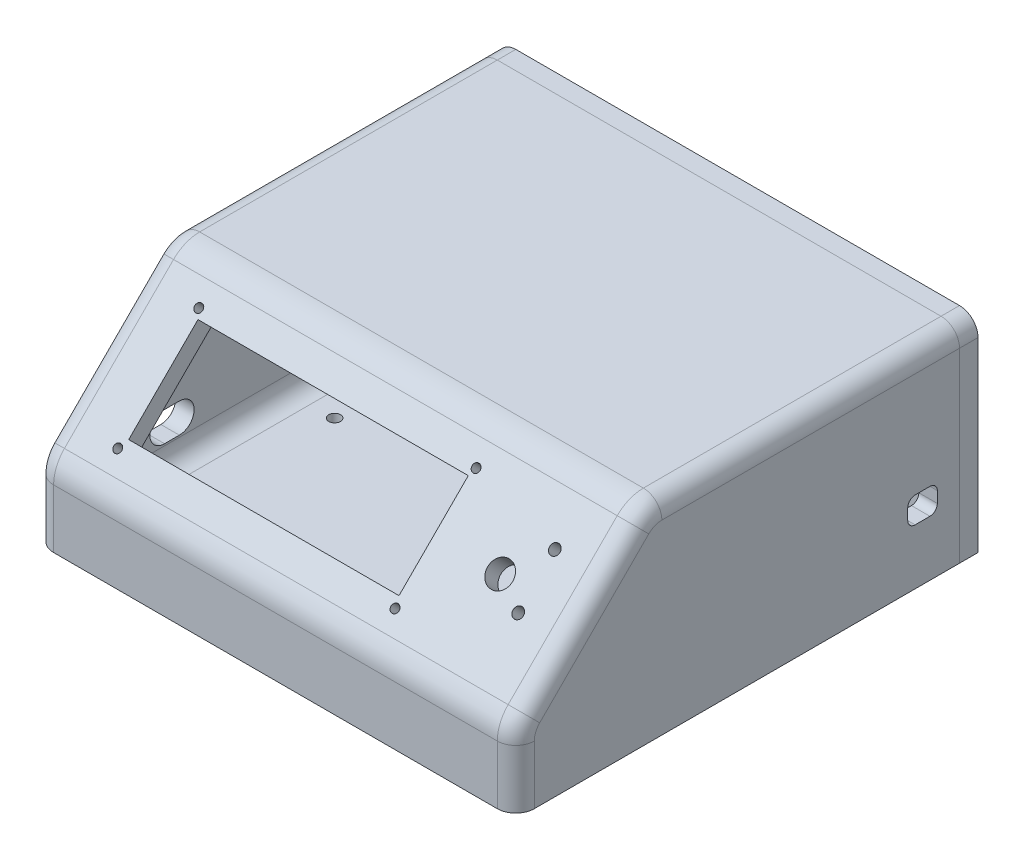
SolidWorks part; units mm, degrees
ref_plane "Front Plane" through (0, 0, 0) normal (0, 0, 1) x (1, 0, 0)
ref_plane "Top Plane" through (0, 0, 0) normal (0, 1, 0) x (1, 0, 0)
ref_plane "Right Plane" through (0, 0, 0) normal (1, 0, 0) x (0, 0, -1)
sketch "Sketch2" plane through (0, 0, 0) normal (1, 0, 0) x (0, 0, -1)
  line L0 (0, 0) -> (0, 20)
  line L1 (0, 20) -> (35.3553, 55.3553)
  line L2 (35.3553, 55.3553) -> (120, 55.3553)
  line L3 (120, 55.3553) -> (120, 0)
  line L4 (120, 0) -> (0, 0)
  dimension "D1" = 20
  dimension "D2" = 50
  dimension "D3" = 135
  dimension "D4" = 120
extrude "Boss-Extrude1" add sketch "Sketch2" along normal blind 130
shell "Shell1" thickness 5 removed face at (65, 27.6777, -120)
sketch "Sketch3" plane through (0, 10, 10) normal (0, 0.7071, 0.7071) x (1, 0, 0)
  line L0 (0, 64.1421) -> (0, 14.1421) construction
  line L1 (17, 52.3921) -> (90.1, 52.3921)
  line L2 (17, 52.3921) -> (17, 25.8921)
  line L3 (17, 25.8921) -> (90.1, 25.8921)
  line L4 (90.1, 52.3921) -> (90.1, 25.8921)
  circle A0 centre (108.1, 39.1421) radius 3.4
  point P6 (0, 39.1421)
  point P7 (17, 39.1421)
  point P11 (90.1, 39.1421)
  dimension "D3" = 6.8
  dimension "D1" = 73.1
  dimension "D2" = 26.5
  dimension "D4" = 18
  dimension "D5" = 17
extrude "Cut-Extrude1" cut sketch "Sketch3" against normal up to surface (5 mm away) up to face at (65, 34.1421, -21.2132)
fillet "Fillet1" radius 10 5 edges at (65, 20, 0) (65, 55.3553, -35.3553) (65, 50.3553, -37.4264) (65, 5, -5) (65, 17.9289, -5)
fillet "Fillet2" radius 5 10 edges at (0, 55.3553, -79.7487) (0, 54.5941, -35.6706) (0, 37.6777, -17.6777) (0, 19.6847, -0.7612) (130, 55.3553, -79.7487) (130, 54.5941, -35.6706) (130, 37.6777, -17.6777) (130, 19.6847, -0.7612) (0, 7.9289, 0) (130, 7.9289, 0)
sketch "Sketch4" plane through (130, 0, 0) normal (1, 0, 0) x (0, 0, -1)
  line L0 (5, 0) -> (120, 0) construction
  line L1 (108, 22) -> (112, 22)
  line L2 (106, 20) -> (106, 17)
  line L3 (108, 15) -> (112, 15)
  line L4 (114, 20) -> (114, 17)
  line L5 (120, 0) -> (120, 50.3553) construction
  arc A0 (106, 17) -> (108, 15) centre (108, 17) ccw
  arc A1 (112, 15) -> (114, 17) centre (112, 17) ccw
  arc A2 (112, 22) -> (114, 20) centre (112, 20) cw
  arc A3 (108, 22) -> (106, 20) centre (108, 20) ccw
  point P8 (114, 15)
  point P11 (114, 22)
  point P14 (106, 22)
  point P15 (63.3615, 10.7328)
  dimension "D3" = 2
  dimension "D1" = 8
  dimension "D2" = 7
  dimension "D4" = 15
  dimension "D5" = 6
extrude "Cut-Extrude2" cut sketch "Sketch4" against normal up to surface (5 mm away) up to face at (125, 27.4827, -48.7525)
fillet "Fillet3" radius 5 12 edges at (125, 7.7176, -8.1468) (125, 17.8922, -5.8816) (125, 34.1421, -21.2132) (125, 49.5941, -37.7417) (5, 7.7176, -8.1468) (5, 17.8922, -5.8816) (5, 34.1421, -21.2132) (5, 49.5941, -37.7417) (125, 5, -67.5) (125, 50.3553, -80.7843) (5, 5, -67.5) (5, 50.3553, -80.7843)
sketch "Sketch5" plane through (0, 10, 10) normal (0, 0.7071, 0.7071) x (1, 0, 0)
  line L0 (102.2, 33.1421) -> (114, 45.1421) construction
  line L1 (102.2, 45.1421) -> (114, 45.1421) construction
  line L2 (102.2, 45.1421) -> (102.2, 33.1421) construction
  line L3 (102.2, 33.1421) -> (114, 33.1421) construction
  line L4 (114, 45.1421) -> (114, 33.1421) construction
  line L6 (99.8, 55.0421) -> (118.6, 55.0421) construction
  line L7 (99.8, 55.0421) -> (99.8, 28.7421) construction
  line L8 (99.8, 28.7421) -> (118.6, 28.7421) construction
  line L9 (118.6, 55.0421) -> (118.6, 28.7421) construction
  circle A0 centre (108.1, 39.1421) radius 3.4 construction
  circle A1 centre (108.1, 39.1421) radius 3.4 construction
  circle A2 centre (116.3, 48.4421) radius 1.4
  circle A3 centre (116.3, 34.4421) radius 1.4
  point P8 (108.1, 39.1421)
  point P16 (0, 0)
  point P17 (117.3153, 34.7801)
  dimension "D7" = 2.8
  dimension "D1" = 12
  dimension "D2" = 11.8
  dimension "D3" = 2.4
  dimension "D4" = 18.8
  dimension "D5" = 26.3
  dimension "D6" = 4.4
  dimension "D8" = 14
  dimension "D9" = 5.7
  dimension "D10" = 16.5
extrude "Cut-Extrude3" cut sketch "Sketch5" against normal up to next
sketch "Sketch6" plane through (0, 10, 10) normal (0, 0.7071, 0.7071) x (1, 0, 0)
  line L0 (90.1, 52.3921) -> (17, 52.3921) construction
  line L1 (13.3, 57.3921) -> (93.8, 57.3921) construction
  line L2 (13.3, 57.3921) -> (13.3, 20.8921) construction
  line L3 (13.3, 20.8921) -> (93.8, 20.8921) construction
  line L4 (93.8, 57.3921) -> (93.8, 20.8921) construction
  line L5 (17, 52.3921) -> (17, 25.8921) construction
  circle A0 centre (15.8, 54.3921) radius 1.1
  circle A1 centre (90.8, 54.3921) radius 1.1
  circle A2 centre (90.8, 23.3921) radius 1.1
  circle A3 centre (15.8, 23.3921) radius 1.1
  point P16 (13.3, 39.1421)
  point P17 (17, 39.1421)
  point P18 (101.5602, 57.3921)
  point P19 (53.55, 57.3921)
  point P20 (53.55, 52.3921)
  point P21 (0, 0)
  point P23 (0, 0)
  dimension "D3" = 2.2
  dimension "D1" = 75
  dimension "D2" = 31
  dimension "D4" = 5
  dimension "D5" = 3.7
  dimension "D6" = 3
  dimension "D7" = 2.5
extrude "Cut-Extrude4" cut sketch "Sketch6" against normal up to next
sketch "Sketch7" plane through (0, 5, 0) normal (0, 1, 0) x (1, 0, 0)
  line L0 (109.5, 21.5) -> (113, 21.5) construction
  line L1 (113, 18) -> (13, 18) construction
  line L2 (113, 18) -> (113, 68) construction
  line L3 (113, 68) -> (13, 68) construction
  line L4 (13, 18) -> (13, 68) construction
  line L5 (109.5, 21.5) -> (109.5, 18) construction
  line L7 (16.5, 21.5) -> (13, 21.5) construction
  line L8 (16.5, 21.5) -> (16.5, 18) construction
  line L9 (109.5, 64.5) -> (109.5, 68) construction
  line L10 (10, 120) -> (10, 15) construction
  line L11 (10, 15) -> (120, 15) construction
  line L12 (120, 120) -> (10, 120) construction
  line L13 (111, 77) -> (51, 77) construction
  line L14 (111, 77) -> (111, 117) construction
  line L15 (111, 117) -> (51, 117) construction
  line L16 (51, 77) -> (51, 117) construction
  line L17 (109, 79) -> (109, 77) construction
  line L18 (109, 79) -> (111, 79) construction
  line L19 (53, 79) -> (51, 79) construction
  line L20 (109, 115) -> (109, 117) construction
  circle A0 centre (16.5, 21.5) radius 1.5
  circle A1 centre (16.5, 64.5) radius 1.5
  circle A2 centre (109.5, 21.5) radius 1.5
  circle A3 centre (109.5, 64.5) radius 1.5
  circle A4 centre (109, 79) radius 1.5
  circle A5 centre (53, 79) radius 1.5
  circle A6 centre (53, 115) radius 1.5
  circle A7 centre (109, 115) radius 1.5
  dimension "D1" = 3
  dimension "D12" = 2
  dimension "D2" = 43
  dimension "D3" = 93
  dimension "D4" = 100
  dimension "D5" = 50
  dimension "D6" = 3
  dimension "D7" = 3
  dimension "D8" = 40
  dimension "D9" = 60
  dimension "D10" = 2
  dimension "D11" = 3
  dimension "D13" = 2
extrude "Cut-Extrude5" cut sketch "Sketch7" against normal up to next
hole_wizard "CSK for M3 Countersunk Flat Head Screw2" positions "Sketch12" profile "Sketch13" countersink size "M3" standard "ISO"
sketch "Sketch12" plane through (0, 0, 0) normal (0, -1, 0) x (-1, 0, 0)
  point P0 (-109, 115)
  point P3 (-53, 115)
  point P6 (-53, 79)
  point P9 (-109, 79)
  point P12 (-16.5, 64.5)
  point P15 (-16.5, 21.5)
  point P18 (-109.5, 21.5)
  point P21 (-109.5, 64.5)
sketch "Sketch13" plane through (109, 0, -115) normal (1, 0, 0) x (0, 0, -1)
  line L0 (0, 0) -> (0, 8.9614)
  line L1 (0, 8.9614) -> (1.6, 8)
  line L2 (1.6, 8) -> (1.6, 1.55)
  line L3 (1.6, 1.55) -> (3.15, 0)
  line L5 (3.15, 0) -> (0, 0)
  line L6 (-1.6, 1.55) -> (-3.15, 0) construction
  line L10 (0, 8.9614) -> (-1.6, 8) construction
  line L11 (0, -6.35) -> (0, 107.95) construction
  dimension "Hole Dia." = 3.2
  dimension "Hole Depth" = 8
  dimension "Near C'Sink Dia." = 6.3
  dimension "Near C'Sink Angle" = 90
  dimension "Drill Angle" = 118
sketch "Sketch14" plane through (0, 0, 0) normal (-1, 0, 0) x (0, 0, 1)
  line L0 (-34, 14.5) -> (-30, 14.5) construction
  line L1 (-34, 18.5) -> (-30, 18.5)
  line L2 (-34, 10.5) -> (-30, 10.5)
  line L3 (-5, 0) -> (-120, 0) construction
  line L4 (-120, 0) -> (-120, 50.3553) construction
  line L5 (-19.9, 5) -> (-23.1, 5) construction
  line L6 (-19.9, 5) -> (-23.1, 5) construction
  arc A0 (-34, 18.5) -> (-34, 10.5) centre (-34, 14.5) ccw
  arc A1 (-30, 10.5) -> (-30, 18.5) centre (-30, 14.5) ccw
  point P2 (-32, 14.5)
  dimension "D1" = 4
  dimension "D2" = 4
  dimension "D3" = 14.5
  dimension "D4" = 86
extrude "Cut-Extrude6" cut sketch "Sketch14" against normal up to next
sketch "Sketch15" plane through (0, 0, -120) normal (0, 0, -1) x (-1, 0, 0)
  line L0 (-125, 55.3553) -> (-5, 55.3553) construction
  line L1 (-130, 0) -> (-130, 50.3553) construction
  line L2 (0, 0) -> (0, 50.3553) construction
  line L3 (-130, 0) -> (0, 0) construction
  circle A0 centre (-126, 51.3553) radius 1.2
  circle A1 centre (-126, 4) radius 1.2
  circle A2 centre (-4, 4) radius 1.2
  circle A3 centre (-4, 51.3553) radius 1.2
  point P8 (0, 0)
  point P9 (0, 0)
  point P10 (0, 0)
  point P11 (0, 0)
  point P12 (0, 0)
  dimension "D1" = 2.4
  dimension "D2" = 4
  dimension "D3" = 4
  dimension "D4" = 4
  dimension "D5" = 4
extrude "Cut-Extrude7" cut sketch "Sketch15" against normal blind 20
sketch "Sketch16" plane through (0, 0, -120) normal (0, 0, -1) x (-1, 0, 0)
  line L4 (0, 0) -> (0, 50.3553)
  line L5 (-5, 55.3553) -> (-125, 55.3553)
  line L6 (-130, 50.3553) -> (-130, 0)
  line L7 (-130, 0) -> (0, 0)
  line L8 (0, 0) -> (0, 50.3553)
  line L9 (-5, 55.3553) -> (-125, 55.3553)
  line L10 (-130, 50.3553) -> (-130, 0)
  line L11 (-130, 0) -> (0, 0)
  circle A0 centre (-126, 4) radius 1.2 construction
  circle A1 centre (-4, 4) radius 1.2 construction
  arc A2 (0, 50.3553) -> (-5, 55.3553) centre (-5, 50.3553) ccw
  arc A3 (-125, 55.3553) -> (-130, 50.3553) centre (-125, 50.3553) ccw
  arc A4 (0, 50.3553) -> (-5, 55.3553) centre (-5, 50.3553) ccw
  arc A5 (-125, 55.3553) -> (-130, 50.3553) centre (-125, 50.3553) ccw
  circle A6 centre (-4, 51.3553) radius 1.2 construction
  circle A7 centre (-126, 51.3553) radius 1.2 construction
  circle A8 centre (-126, 4) radius 1.2
  circle A9 centre (-4, 4) radius 1.2
  circle A10 centre (-4, 51.3553) radius 1.2
  circle A11 centre (-126, 51.3553) radius 1.2
  dimension "D1" = 0
extrude "Boss-Extrude2" add sketch "Sketch16" along normal blind 5 separate body
hole_wizard "CSK for M3 Countersunk Flat Head Screw3" positions "Sketch19" profile "Sketch20" countersink size "M3" standard "ISO"
sketch "Sketch19" plane through (0, 0, -125) normal (0, 0, -1) x (-1, 0, 0)
  point P0 (-126, 51.3553)
  point P3 (-126, 4)
  point P6 (-4, 51.3553)
  point P9 (-4, 4)
sketch "Sketch20" plane through (126, 51.3553, -125) normal (1, 0, 0) x (0, 1, 0)
  line L0 (0, 0) -> (0, 8.9614)
  line L1 (0, 8.9614) -> (1.6, 8)
  line L2 (1.6, 8) -> (1.6, 1.55)
  line L3 (1.6, 1.55) -> (3.15, 0)
  line L5 (3.15, 0) -> (0, 0)
  line L6 (-1.6, 1.55) -> (-3.15, 0) construction
  line L10 (0, 8.9614) -> (-1.6, 8) construction
  line L11 (0, -6.35) -> (0, 107.95) construction
  dimension "Hole Dia." = 3.2
  dimension "Hole Depth" = 8
  dimension "Near C'Sink Dia." = 6.3
  dimension "Near C'Sink Angle" = 90
  dimension "Drill Angle" = 118
